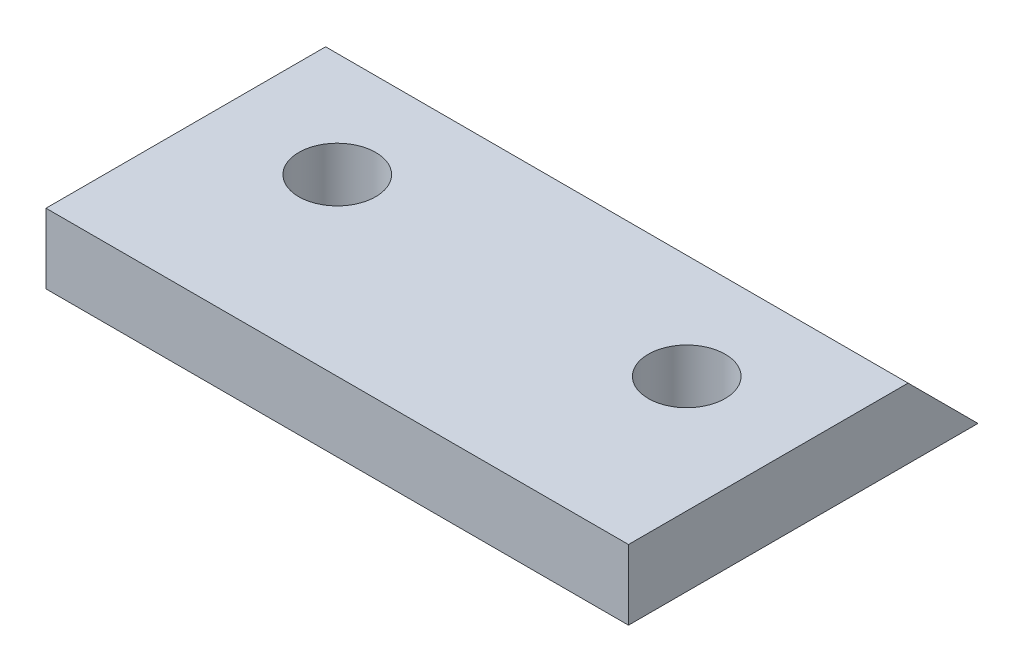
SolidWorks part; units mm, degrees
ref_plane "Front Plane" through (0, 0, 0) normal (0, 0, 1) x (1, 0, 0)
ref_plane "Top Plane" through (0, 0, 0) normal (0, 1, 0) x (1, 0, 0)
ref_plane "Right Plane" through (0, 0, 0) normal (1, 0, 0) x (0, 0, -1)
sketch "Sketch1" plane through (0, 0, 0) normal (0, 1, 0) x (1, 0, 0)
  line L1 (-12.5, -7.5) -> (12.5, -7.5)
  line L2 (-12.5, -7.5) -> (-12.5, 7.5)
  line L3 (-12.5, 7.5) -> (12.5, 7.5)
  line L4 (12.5, -7.5) -> (12.5, 7.5)
  line L5 (-12.5, -7.5) -> (12.5, 7.5) construction
  line L6 (-12.5, 7.5) -> (12.5, -7.5) construction
  point P0 (0, 0)
  dimension "D1" = 25
  dimension "D2" = 15
extrude "Boss-Extrude1" add sketch "Sketch1" along normal blind 3
hole_wizard "M4x0.7 Tapped Hole1" positions "Sketch2" profile "Sketch4" tap size "M4x0.7" standard "ANSI Metric" end condition through all
sketch "Sketch2" plane through (0, 3, 0) normal (0, 1, 0) x (1, 0, 0)
  line L0 (-7.5, 0) -> (7.5, 0)
  point P0 (-7.5, 0)
  point P1 (7.5, 0)
  point P3 (0, 0)
  dimension "D1" = 15
sketch "Sketch4" plane through (-7.5, 3, 0) normal (1, 0, 0) x (0, 0, 1)
  line L0 (0, 0) -> (0, 3)
  line L1 (0, 3) -> (1.65, 3)
  line L2 (1.65, 3) -> (1.65, 0)
  line L5 (1.65, 0) -> (0, 0)
  line L11 (0, -6.35) -> (0, 107.95) construction
  dimension "Thru Tap Drill Dia." = 3.3
  dimension "Thru Tap Drill Depth" = 3
cosmetic thread "Hole Thread1"
cosmetic thread "Hole Thread2"
chamfer "Chamfer1" distance 3 angle 45 1 edges at (0, 3, -7.5)
